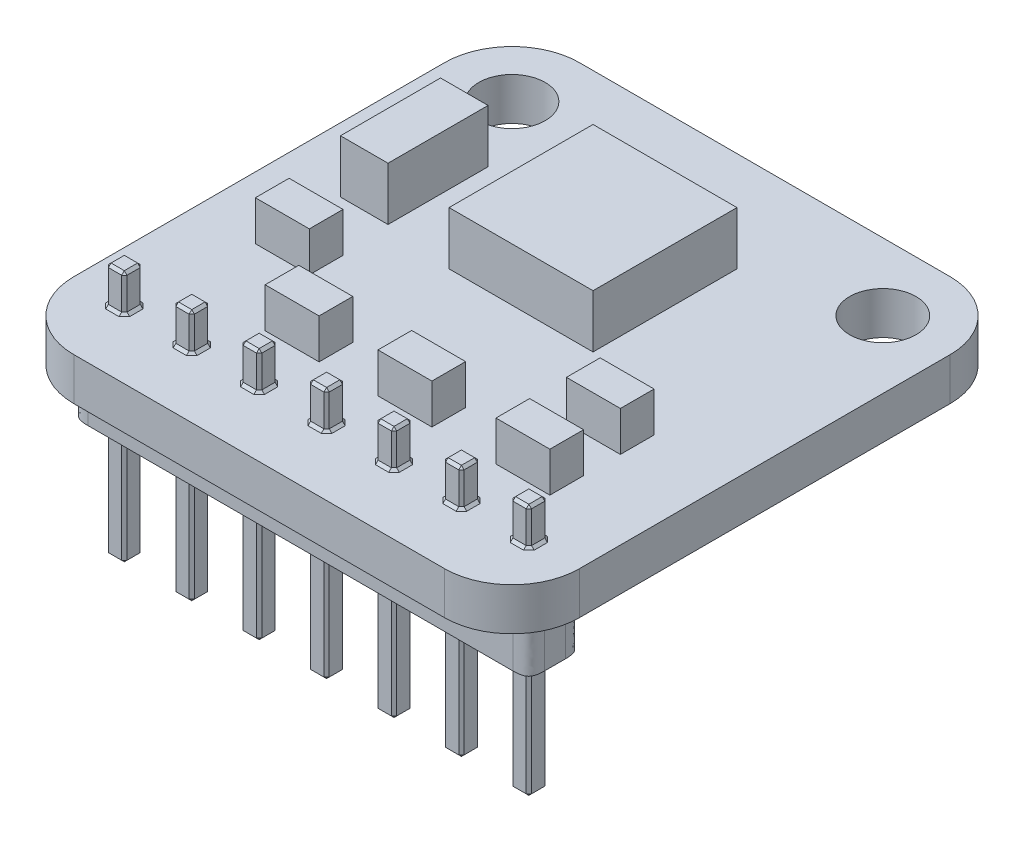
SolidWorks part; units mm, degrees
ref_plane "Front Plane" through (0, 0, 0) normal (0, 0, 1) x (1, 0, 0)
ref_plane "Top Plane" through (0, 0, 0) normal (0, 1, 0) x (1, 0, 0)
ref_plane "Right Plane" through (0, 0, 0) normal (1, 0, 0) x (0, 0, -1)
sketch "Sketch1" plane through (0, 0, 0) normal (0, 1, 0) x (1, 0, 0)
  line L1 (-6.985, 0) -> (6.985, 0)
  line L2 (-9.525, 2.54) -> (-9.525, 16.51)
  line L3 (-6.985, 19.05) -> (6.985, 19.05)
  line L4 (9.525, 2.54) -> (9.525, 16.51)
  line L5 (-9.525, 19.05) -> (-6.985, 19.05) construction
  line L6 (-9.525, 19.05) -> (-9.525, 16.51) construction
  line L7 (-9.525, 16.51) -> (-6.985, 16.51) construction
  line L8 (-6.985, 19.05) -> (-6.985, 16.51) construction
  line L9 (9.525, 19.05) -> (6.985, 19.05) construction
  line L10 (9.525, 19.05) -> (9.525, 16.51) construction
  line L11 (9.525, 16.51) -> (6.985, 16.51) construction
  line L12 (6.985, 19.05) -> (6.985, 16.51) construction
  line L13 (0, 0) -> (0, 50000) construction
  circle A0 centre (-6.985, 16.51) radius 1.25
  circle A1 centre (6.985, 16.51) radius 1.25
  arc A8 (6.985, 0) -> (9.525, 2.54) centre (6.985, 2.54) ccw
  arc A9 (9.525, 16.51) -> (6.985, 19.05) centre (6.985, 16.51) ccw
  arc A10 (-6.985, 19.05) -> (-9.525, 16.51) centre (-6.985, 16.51) ccw
  arc A11 (-9.525, 2.54) -> (-6.985, 0) centre (-6.985, 2.54) ccw
  point P4 (0, 0)
  point P42 (-9.525, 0)
  dimension "D4" = 2.5
  dimension "D12" = 2.54
  dimension "D1" = 19.05
  dimension "D2" = 19.05
  dimension "D3" = 13.97
extrude "Boss-Extrude1" add sketch "Sketch1" along normal blind 1.6 contours L2 A11 L1 A8 L4 A9 L3 A10 A0 A1
sketch "Sketch3" plane through (0, 0, 0) normal (0, -1, 0) x (1, 0, 0)
  line L0 (9.525, -2.54) -> (-7.9647, -2.54) construction
  line L2 (5.43, -2.19) -> (5.43, -2.89)
  line L3 (7.97, -2.19) -> (7.27, -2.19)
  line L4 (7.97, -2.19) -> (7.97, -2.89)
  line L5 (7.97, -2.89) -> (7.27, -2.89)
  line L6 (7.27, -2.19) -> (7.27, -2.89)
  line L7 (7.97, -2.19) -> (7.27, -2.89) construction
  line L8 (7.97, -2.89) -> (7.27, -2.19) construction
  line L9 (5.43, -2.19) -> (4.73, -2.19)
  line L10 (4.73, -2.19) -> (4.73, -2.89)
  line L11 (5.43, -2.89) -> (4.73, -2.89)
  line L12 (2.89, -2.19) -> (2.89, -2.89)
  line L13 (2.89, -2.19) -> (2.19, -2.19)
  line L14 (2.19, -2.19) -> (2.19, -2.89)
  line L15 (2.89, -2.89) -> (2.19, -2.89)
  line L16 (0.35, -2.19) -> (0.35, -2.89)
  line L17 (0.35, -2.19) -> (-0.35, -2.19)
  line L18 (-0.35, -2.19) -> (-0.35, -2.89)
  line L19 (0.35, -2.89) -> (-0.35, -2.89)
  line L20 (-2.19, -2.19) -> (-2.19, -2.89)
  line L21 (-2.19, -2.19) -> (-2.89, -2.19)
  line L22 (-2.89, -2.19) -> (-2.89, -2.89)
  line L23 (-2.19, -2.89) -> (-2.89, -2.89)
  line L24 (-4.73, -2.19) -> (-4.73, -2.89)
  line L25 (-4.73, -2.19) -> (-5.43, -2.19)
  line L26 (-5.43, -2.19) -> (-5.43, -2.89)
  line L27 (-4.73, -2.89) -> (-5.43, -2.89)
  line L28 (-7.27, -2.19) -> (-7.27, -2.89)
  line L29 (-7.27, -2.19) -> (-7.97, -2.19)
  line L30 (-7.97, -2.19) -> (-7.97, -2.89)
  line L31 (-7.27, -2.89) -> (-7.97, -2.89)
  line L32 (0, 0) -> (0, -5.6753) construction
  point P1 (7.62, -2.54)
  point P9 (0, -2.19)
  dimension "D1" = 2.54
  dimension "D2" = 0.7
  dimension "D4" = 2.54
  dimension "D3" = 7
extrude "Boss-Extrude2" add sketch "Sketch3" against normal blind 3 and the other way blind 6.5
sketch "Sketch4" plane through (0, 0, 0) normal (0, -1, 0) x (1, 0, 0)
  line L0 (-7.97, -2.19) -> (-7.97, -2.89) construction
  line L1 (-8.605, -3.53) -> (8.605, -3.53)
  line L2 (-8.605, -3.53) -> (-8.605, -1.55)
  line L3 (-8.605, -1.55) -> (8.605, -1.55)
  line L4 (8.605, -3.53) -> (8.605, -1.55)
  line L5 (-8.605, -3.53) -> (8.605, -1.55) construction
  line L6 (-8.605, -1.55) -> (8.605, -3.53) construction
  line L7 (-7.97, -2.89) -> (-7.27, -2.89) construction
  line L8 (-7.27, -2.54) -> (49992.73, -2.54) construction
  line L9 (-7.27, -2.89) -> (-7.27, -2.19) construction
  point P0 (0, -2.54)
  point P5 (-8.605, -2.54)
  point P15 (-7.27, -2.54)
  dimension "D1" = 0.635
  dimension "D2" = 0.64
extrude "Boss-Extrude3" add sketch "Sketch4" along normal blind 2
sketch "Sketch5" plane through (0, 1.6, 0) normal (0, 1, 0) x (1, 0, 0)
  line L1 (2.7117, 9.8656) -> (-2.7117, 9.8656)
  line L2 (2.7117, 9.8656) -> (2.7117, 15.2889)
  line L3 (2.7117, 15.2889) -> (-2.7117, 15.2889)
  line L4 (-2.7117, 9.8656) -> (-2.7117, 15.2889)
  line L5 (2.7117, 9.8656) -> (-2.7117, 15.2889) construction
  line L6 (2.7117, 15.2889) -> (-2.7117, 9.8656) construction
  point P0 (0, 12.5773)
  point P6 (0, 9.8656)
extrude "Boss-Extrude4" add sketch "Sketch5" along normal blind 2
sketch "Sketch6" plane through (0, 1.6, 0) normal (0, 1, 0) x (1, 0, 0)
  line L1 (-5.1488, 7.0381) -> (-7.1808, 7.0381)
  line L2 (-5.1488, 7.0381) -> (-5.1488, 8.3081)
  line L3 (-5.1488, 8.3081) -> (-7.1808, 8.3081)
  line L4 (-7.1808, 7.0381) -> (-7.1808, 8.3081)
  line L5 (-5.1488, 7.0381) -> (-7.1808, 8.3081) construction
  line L6 (-5.1488, 8.3081) -> (-7.1808, 7.0381) construction
  line L7 (-2.1258, 4.3823) -> (-4.1578, 4.3823)
  line L8 (-2.1258, 4.3823) -> (-2.1258, 5.6523)
  line L9 (-2.1258, 5.6523) -> (-4.1578, 5.6523)
  line L10 (-4.1578, 4.3823) -> (-4.1578, 5.6523)
  line L11 (-2.1258, 4.3823) -> (-4.1578, 5.6523) construction
  line L12 (-2.1258, 5.6523) -> (-4.1578, 4.3823) construction
  line L13 (2.125, 4.3823) -> (0.093, 4.3823)
  line L14 (2.125, 4.3823) -> (2.125, 5.6523)
  line L15 (2.125, 5.6523) -> (0.093, 5.6523)
  line L16 (0.093, 4.3823) -> (0.093, 5.6523)
  line L17 (2.125, 4.3823) -> (0.093, 5.6523) construction
  line L18 (2.125, 5.6523) -> (0.093, 4.3823) construction
  line L19 (6.5693, 4.3823) -> (4.5373, 4.3823)
  line L20 (6.5693, 4.3823) -> (6.5693, 5.6523)
  line L21 (6.5693, 5.6523) -> (4.5373, 5.6523)
  line L22 (4.5373, 4.3823) -> (4.5373, 5.6523)
  line L23 (6.5693, 4.3823) -> (4.5373, 5.6523) construction
  line L24 (6.5693, 5.6523) -> (4.5373, 4.3823) construction
  line L25 (6.5693, 7.0381) -> (4.5373, 7.0381)
  line L26 (6.5693, 7.0381) -> (6.5693, 8.3081)
  line L27 (6.5693, 8.3081) -> (4.5373, 8.3081)
  line L28 (4.5373, 7.0381) -> (4.5373, 8.3081)
  line L29 (6.5693, 7.0381) -> (4.5373, 8.3081) construction
  line L30 (6.5693, 8.3081) -> (4.5373, 7.0381) construction
  point P0 (-6.1648, 7.6731)
  point P5 (-3.1418, 5.0173)
  point P10 (1.109, 5.0173)
  point P15 (5.5533, 5.0173)
  point P20 (5.5533, 7.6731)
  dimension "D1" = 1.27
  dimension "D2" = 2.032
extrude "Boss-Extrude5" add sketch "Sketch6" along normal blind 1.5
sketch "Sketch7" plane through (0, 1.6, 0) normal (0, 1, 0) x (1, 0, 0)
  line L1 (-7.1001, 10.163) -> (-5.3086, 10.163)
  line L2 (-7.1001, 10.163) -> (-7.1001, 13.9326)
  line L3 (-7.1001, 13.9326) -> (-5.3086, 13.9326)
  line L4 (-5.3086, 10.163) -> (-5.3086, 13.9326)
  line L5 (-7.1001, 10.163) -> (-5.3086, 13.9326) construction
  line L6 (-7.1001, 13.9326) -> (-5.3086, 10.163) construction
  point P0 (-6.2044, 12.0478)
extrude "Boss-Extrude6" add sketch "Sketch7" along normal blind 2
fillet "Fillet1" radius 0.6 4 edges at (8.605, -1, -3.53) (8.605, -1, -1.55) (-8.605, -1, -3.53) (-8.605, -1, -1.55)
fillet "Chamfer2" radius 0.1 116 edges at (7.62, 1.6, -2.89) (7.97, 2.3, -2.89) (7.27, 2.3, -2.19) (7.97, 2.3, -2.19) (7.62, 3, -2.89) (7.97, 3, -2.54) (7.27, 3, -2.54) (5.43, 2.3, -2.89) (5.43, 1.6, -2.54) (5.43, 2.3, -2.19) (5.08, 1.6, -2.19) (4.73, 2.3, -2.89) (4.73, 1.6, -2.54) (5.08, 3, -2.19) (2.54, 1.6, -2.89) (2.89, 2.3, -2.89) (2.89, 1.6, -2.54) (2.89, 2.3, -2.19) (2.54, 1.6, -2.19) (2.19, 2.3, -2.89) (2.19, 2.3, -2.19) (2.19, 1.6, -2.54) (2.89, 3, -2.54) (2.19, 3, -2.54) (2.54, 3, -2.89) (0, 1.6, -2.89) (0.35, 2.3, -2.89) (0.35, 1.6, -2.54) (0.35, 2.3, -2.19) (0, 1.6, -2.19) (-0.35, 2.3, -2.89) (-0.35, 2.3, -2.19) (-0.35, 1.6, -2.54) (0.35, 3, -2.54) (0, 3, -2.19) (0, 3, -2.89) (-2.54, 1.6, -2.89) (-2.19, 2.3, -2.89) (-2.19, 1.6, -2.54) (-2.19, 2.3, -2.19) (-2.54, 1.6, -2.19) (-2.89, 2.3, -2.19) (-2.54, 3, -2.19) (-2.54, 3, -2.89) (-5.08, 1.6, -2.89) (-4.73, 2.3, -2.89) (-4.73, 2.3, -2.19) (-5.08, 1.6, -2.19) (-5.43, 2.3, -2.89) (-5.43, 2.3, -2.19) (-4.73, 3, -2.54) (-5.08, 3, -2.19) (-5.43, 3, -2.54) (-7.62, 1.6, -2.89) (-7.27, 2.3, -2.89) (-7.27, 1.6, -2.54) (-7.27, 2.3, -2.19) (-7.62, 1.6, -2.19) (-7.97, 2.3, -2.19) (-7.62, 3, -2.19) (-7.97, 3, -2.54) (-7.62, 3, -2.89) (-7.62, -2, -2.89) (-7.27, -4.25, -2.89) (-7.27, -6.5, -2.54) (-7.27, -4.25, -2.19) (-7.62, -6.5, -2.19) (-7.62, -2, -2.19) (-7.97, -4.25, -2.19) (-7.97, -6.5, -2.54) (-7.97, -2, -2.54) (-5.08, -6.5, -2.89) (-5.08, -2, -2.89) (-4.73, -4.25, -2.89) (-4.73, -6.5, -2.54) (-4.73, -4.25, -2.19) (-5.08, -6.5, -2.19) (-5.08, -2, -2.19) (-5.43, -4.25, -2.19) (-5.43, -6.5, -2.54) (-5.43, -4.25, -2.89) (-5.43, -2, -2.54) (-2.19, -4.25, -2.89) (-2.19, -2, -2.54) (-2.54, -6.5, -2.19) (-2.89, -4.25, -2.19) (-2.89, -4.25, -2.89) (0, -6.5, -2.89) (0, -2, -2.89) (0.35, -4.25, -2.89) (0.35, -4.25, -2.19) (0, -6.5, -2.19) (0, -2, -2.19) (-0.35, -6.5, -2.54) (2.54, -6.5, -2.89) (2.54, -2, -2.89) (2.89, -6.5, -2.54) (2.89, -4.25, -2.19) (2.54, -2, -2.19) (2.19, -2, -2.54) (5.08, -6.5, -2.89) (5.08, -2, -2.89) (5.43, -4.25, -2.89) (5.43, -6.5, -2.54) (5.43, -2, -2.54) (5.08, -6.5, -2.19) (4.73, -4.25, -2.19) (4.73, -6.5, -2.54) (4.73, -2, -2.54) (7.27, -4.25, -2.89) (7.62, -6.5, -2.89) (7.62, -2, -2.89) (7.97, -4.25, -2.89) (7.97, -2, -2.54) (7.97, -4.25, -2.19) (7.62, -2, -2.19)
